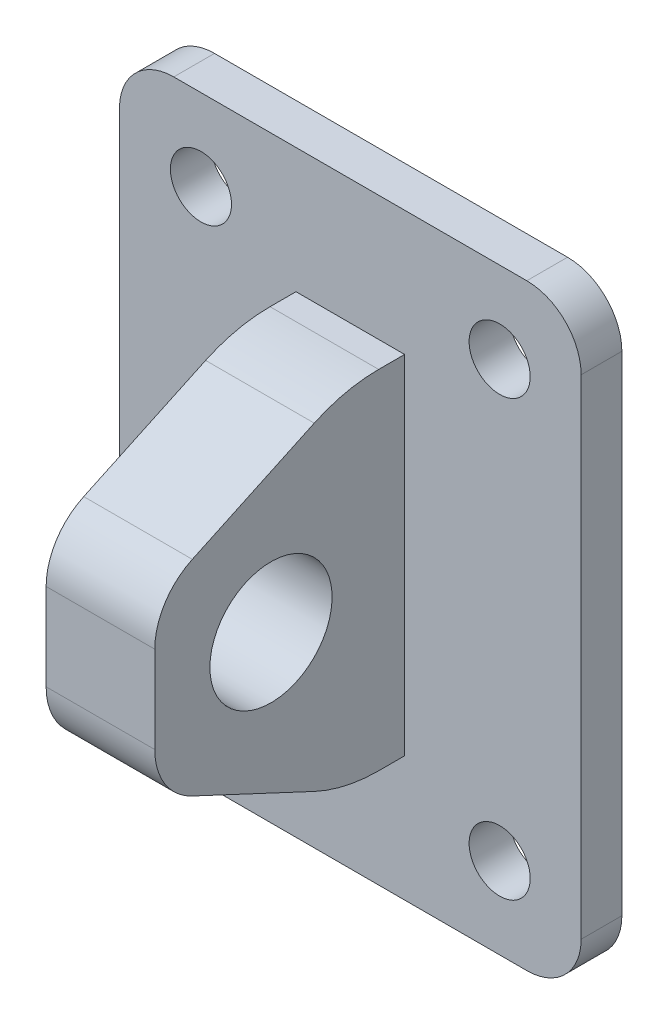
SolidWorks part; units mm, degrees
material "Plain Carbon Steel"
ref_plane "Front Plane" through (0, 0, 0) normal (0, 0, 1) x (1, 0, 0)
ref_plane "Top Plane" through (0, 0, 0) normal (0, 1, 0) x (1, 0, 0)
ref_plane "Right Plane" through (0, 0, 0) normal (1, 0, 0) x (0, 0, -1)
sketch "Sketch1" plane through (0, 0, 0) normal (0, 0, 1) x (1, 0, 0)
  line L9 (-41.275, 69.85) -> (41.275, 69.85)
  line L10 (-53.975, 57.15) -> (-53.975, -57.15)
  line L11 (-41.275, -69.85) -> (41.275, -69.85)
  line L12 (53.975, 57.15) -> (53.975, -57.15)
  line L14 (34.925, -50.8) -> (-34.925, -50.8) construction
  line L19 (34.925, -50.8) -> (34.925, 50.8) construction
  line L20 (34.925, 50.8) -> (-34.925, 50.8) construction
  line L21 (-34.925, -50.8) -> (-34.925, 50.8) construction
  arc A0 (41.275, -69.85) -> (53.975, -57.15) centre (41.275, -57.15) ccw
  arc A1 (-53.975, -57.15) -> (-41.275, -69.85) centre (-41.275, -57.15) ccw
  arc A2 (41.275, 69.85) -> (53.975, 57.15) centre (41.275, 57.15) cw
  arc A3 (-41.275, 69.85) -> (-53.975, 57.15) centre (-41.275, 57.15) ccw
  circle A4 centre (-34.925, 50.8) radius 7.1438
  circle A5 centre (34.925, 50.8) radius 7.1438
  circle A6 centre (-34.925, -50.8) radius 7.1438
  circle A7 centre (34.925, -50.8) radius 7.1438
  point P2 (53.975, -69.85)
  point P6 (-53.975, -69.85)
  point P7 (0, 69.85)
  point P14 (-53.975, 69.85)
  point P16 (0, -69.85)
  point P17 (-53.975, 0)
  dimension "D5" = 14.2875
  dimension "D6" = 12.7
  dimension "D1" = 139.7
  dimension "D2" = 107.95
  dimension "D3" = 19.05
  dimension "D4" = 19.05
  dimension "D7" = 101.6
  dimension "D8" = 69.85
sheet metal parameters "Sheet-Metal1" thickness 9.525 parameters "D1"=0.7366
base flange "Base-Flange1" sketch "Sketch1" thickness 9.525 reverse thickness direction no parameters "D1"=0.7366
ref_plane "Plane1" through (0, 0, 0) normal (-1, 0, 0) x (0, 0, 1)
sketch "Sketch3" plane through (0, 0, 0) normal (-1, 0, 0) x (0, 0, 1)
  line B0 (21.1285, -37.2932) -> (49.6346, -23.9656)
  line B1 (58.42, -10.16) -> (58.42, 10.16)
  line B2 (49.6346, 23.9656) -> (21.1285, 37.2932)
  line B3 (6.0678, 40.64) -> (0, 40.64)
  line B4 (0, 40.64) -> (0, -40.64)
  line B5 (0, -40.64) -> (6.0678, -40.64)
  circle B6 centre (31.242, 0) radius 14.2875
  arc B7 (49.6346, -23.9656) -> (58.42, -10.16) centre (43.18, -10.16) ccw
  arc B8 (58.42, 10.16) -> (49.6346, 23.9656) centre (43.18, 10.16) ccw
  arc B9 (21.1285, 37.2932) -> (6.0678, 40.64) centre (6.0678, 5.08) ccw
  arc B10 (6.0678, -40.64) -> (21.1285, -37.2932) centre (6.0678, -5.08) ccw
sketch_block_instance "dring profile-1"
sketch_block "dring profile"
extrude "Boss-Extrude1" add sketch "Sketch3" along normal blind 12.7 and the other way blind 12.7
split "Split1" bodies to split 102 resulting bodies 103 104 split by face at (0, 0, 0)
sketch "Sketch4" plane through (-12.7, 0, 0) normal (-1, 0, 0) x (0, 0, 1)
  line B0 (58.42, -10.16) -> (58.42, 10.16)
  line B1 (49.6346, 23.9656) -> (21.1285, 37.2932)
  line B2 (6.0678, 40.64) -> (0, 40.64)
  line B3 (0, 40.64) -> (0, -40.64)
  line B4 (0, -40.64) -> (6.0678, -40.64)
  line B5 (21.1285, -37.2932) -> (49.6346, -23.9656)
  circle B6 centre (31.242, 0) radius 14.2875
  arc B7 (49.6346, -23.9656) -> (58.42, -10.16) centre (43.18, -10.16) ccw
  arc B8 (58.42, 10.16) -> (49.6346, 23.9656) centre (43.18, 10.16) ccw
  arc B9 (21.1285, 37.2932) -> (6.0678, 40.64) centre (6.0678, 5.08) ccw
  arc B10 (6.0678, -40.64) -> (21.1285, -37.2932) centre (6.0678, -5.08) ccw
sketch_block_instance "Block1-1"
sketch_block "Block1"
flat pattern "Flat-Pattern1" [suppressed]
sketch "Bend-Lines1" plane through (0, 0, 0) normal (0, 1, 0) x (1, 0, 0)
sketch3d "Bounding-Box1" [suppressed]
  line L0 (0, -12.7, 0) -> (0, 127, 0) construction
  line L1 (-107.95, -12.7, 0) -> (-107.95, 127, 0) construction
  line L2 (0, -12.7, 0) -> (-107.95, -12.7, 0) construction
  line L3 (0, 127, 0) -> (-107.95, 127, 0) construction
